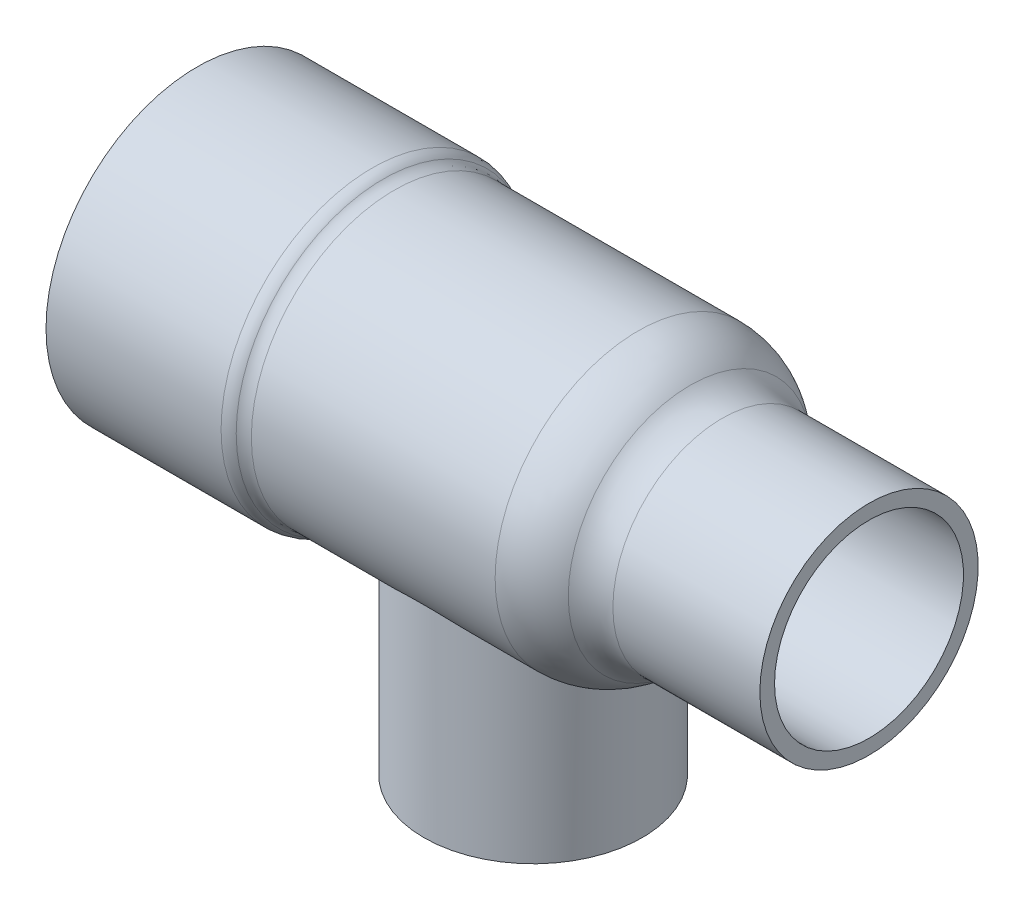
SolidWorks part; units mm, degrees
material "Copper"
ref_plane "Front Plane" through (0, 0, 0) normal (0, 0, 1) x (1, 0, 0)
ref_plane "Top Plane" through (0, 0, 0) normal (0, 1, 0) x (1, 0, 0)
ref_plane "Right Plane" through (0, 0, 0) normal (1, 0, 0) x (0, 0, -1)
sketch "Sketch1" plane through (0, 0, 0) normal (0, 0, 1) x (1, 0, 0)
  line L0 (0, 0) -> (101.6, 0) construction
  line L1 (0, 20.6375) -> (25.4, 20.6375)
  line L2 (25.4, 20.6375) -> (25.4, 19.3929)
  line L3 (25.4, 19.3929) -> (66.675, 19.3929)
  line L5 (79.375, 14.2875) -> (101.6, 14.2875)
  arc A0 (66.675, 19.3929) -> (73.025, 16.8402) centre (66.675, 10.2185) cw
  arc A1 (73.025, 16.8402) -> (79.375, 14.2875) centre (79.375, 23.4619) ccw
  point P8 (75.5597, 16.8402)
  point P10 (70.5216, 19.3929)
  point P12 (0, 0)
  point P13 (0, 0)
  point P14 (0, 0)
  point P20 (67.58, 19.3929)
  dimension "D2" = 41.275
  dimension "D1" = 101.6
  dimension "D3" = 28.575
  dimension "D4" = 25.4
  dimension "D6" = 38.7858
  dimension "D7" = 79.375
  dimension "D5" = 12.7
revolve "Revolve-Thin1" add sketch "Sketch1" angle 360 about L0 wall 2.2225
sketch "Sketch2" plane through (0, 0, 0) normal (0, 1, 0) x (1, 0, 0)
  circle A0 centre (50.8, 0) radius 14.2875
  circle A1 centre (50.8, 0) radius 16.51
  point P3 (42.767, 0.9513)
  dimension "D1" = 28.575
  dimension "D3" = 33.02
  dimension "D2" = 50.8
extrude "Cut-Extrude1" cut sketch "Sketch2" against normal through all contours A0 region at (50.8, 0, 0)
extrude "Boss-Extrude1" add sketch "Sketch2<3>" along normal up to next from offset 44.45 contours A1 A0 region at (34.757, 0, 0) offset against normal yes
sketch "Sketch2<3>" plane through (0, 0, 0) normal (0, 1, 0) x (1, 0, 0) same geometry as "Sketch2"
fillet "Fillet2" radius 2.54 2 edges at (25.4, 0, 20.6375) (27.6225, 0, 21.6154)
fillet "Fillet3" radius 2.54 2 edges at (27.6225, 0, 22.86) (25.4, 0, 19.3929)
